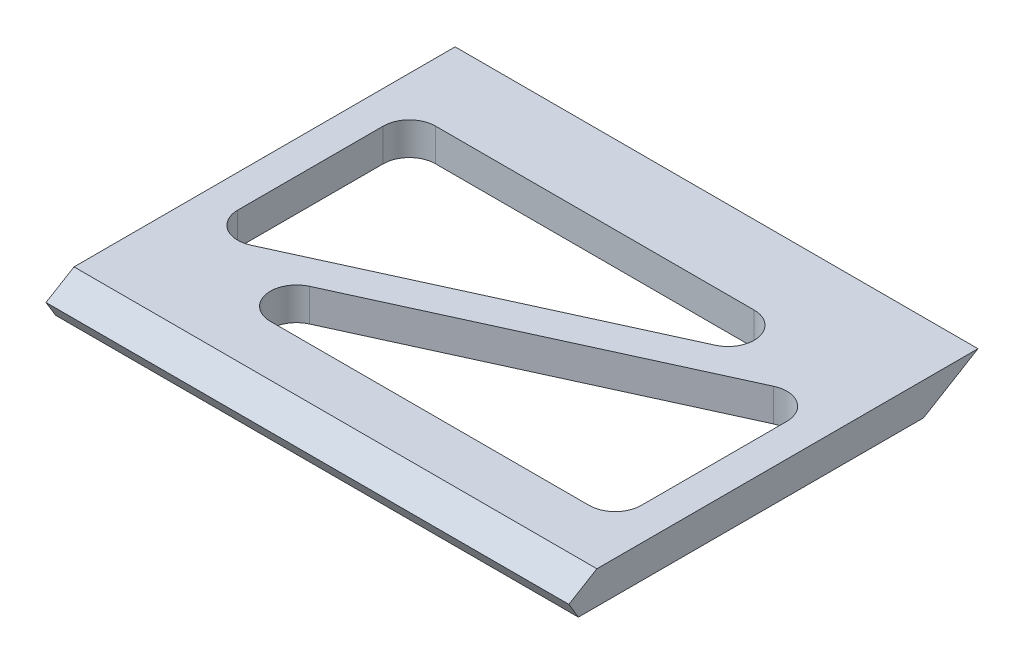
SolidWorks part; units mm, degrees
material "Balsa"
ref_plane "Front Plane" through (0, 0, 0) normal (0, 0, 1) x (1, 0, 0)
ref_plane "Top Plane" through (0, 0, 0) normal (0, 1, 0) x (1, 0, 0)
ref_plane "Right Plane" through (0, 0, 0) normal (1, 0, 0) x (0, 0, -1)
sketch "Sketch3" plane through (71.1933, 0, 0) normal (1, 0, 0) x (0, 0, -1)
  line L0 (56.968, 6.35) -> (46.3846, 0)
  line L1 (46.3846, 0) -> (-20.6804, 0)
  line L2 (-20.6804, 0) -> (-22.5302, 3.083)
  line L3 (-22.5302, 3.083) -> (-32.9848, 20.5072) construction
  line L6 (-22.5302, 3.083) -> (-17.0851, 6.35)
  line L7 (-17.0851, 6.35) -> (56.968, 6.35)
extrude "Boss-Extrude2" add sketch "Sketch3" against normal up to surface (101.6 mm away)
sketch "Sketch4" plane through (0, 6.35, 0) normal (0, 1, 0) x (1, 0, 0)
  line L0 (-30.4067, -17.0851) -> (-30.4067, 56.968) construction
  line L1 (-18.9767, 41.728) -> (42.949, 41.728)
  line L2 (-24.0567, 36.648) -> (-24.0567, 8.3732)
  line L3 (-2.1624, -7.1791) -> (59.7633, -7.1791)
  line L4 (64.8433, 26.1757) -> (64.8433, -2.0991)
  line L5 (-30.4067, 56.968) -> (71.1933, 56.968) construction
  line L6 (71.1933, 56.968) -> (71.1933, -17.0851) construction
  line L7 (-30.4067, -17.0851) -> (71.1933, -17.0851) construction
  line L8 (-16.8668, 3.7521) -> (45.0589, 32.0269)
  line L9 (-4.2724, 2.522) -> (57.6533, 30.7968)
  line L10 (-29.6117, -5.5575) -> (68.6464, 39.3064)
  arc A0 (-4.2724, 2.522) -> (-2.1624, -7.1791) centre (-2.1624, -2.0991) ccw
  arc A1 (59.7633, -7.1791) -> (64.8433, -2.0991) centre (59.7633, -2.0991) ccw
  arc A2 (57.6533, 30.7968) -> (64.8433, 26.1757) centre (59.7633, 26.1757) cw
  arc A3 (45.0589, 32.0269) -> (42.949, 41.728) centre (42.949, 36.648) ccw
  arc A4 (-18.9767, 41.728) -> (-24.0567, 36.648) centre (-18.9767, 36.648) ccw
  arc A5 (-16.8668, 3.7521) -> (-24.0567, 8.3732) centre (-18.9767, 8.3732) cw
  dimension "D7" = 5.08
  dimension "D1" = 6.35
  dimension "D2" = 15.24
  dimension "D3" = 6.35
  dimension "D4" = 9.906
  dimension "D5" = 3.175
  dimension "D6" = 3.175
extrude "Cut-Extrude1" cut sketch "Sketch4" against normal up to surface (6.35 mm away) contours A5 L8 A3 L1 A4 L2 | A2 L9 A0 L3 A1 L4 region at (4.1335, 6.35, -27.6167) region at (36.6531, 6.35, -6.9321) up to face at (20.3933, 0, -12.8521)
